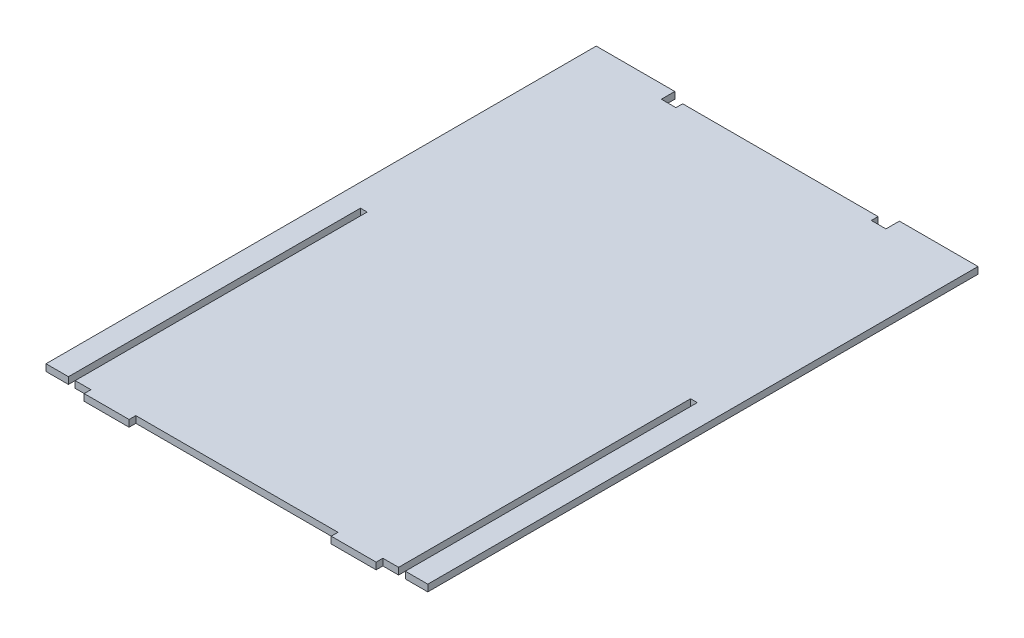
SolidWorks part; units mm, degrees
ref_plane "Front Plane" through (0, 0, 0) normal (0, 0, 1) x (1, 0, 0)
ref_plane "Top Plane" through (0, 0, 0) normal (0, 1, 0) x (1, 0, 0)
ref_plane "Right Plane" through (0, 0, 0) normal (1, 0, 0) x (0, 0, -1)
sketch "Sketch1" plane through (0, 0, 0) normal (0, 1, 0) x (1, 0, 0)
  line L0 (300, 0) -> (300, -6)
  line L2 (0, 0) -> (0, 490)
  line L3 (0, 490) -> (340, 490)
  line L4 (340, 0) -> (340, 490)
  line L5 (300, -6) -> (260, -6)
  line L6 (260, -6) -> (260, 0)
  line L7 (40, 0) -> (40, -6)
  line L8 (40, -6) -> (80, -6)
  line L9 (80, -6) -> (80, 0)
  line L10 (40, 0) -> (0, 0)
  line L11 (80, 0) -> (260, 0)
  line L12 (300, 0) -> (340, 0)
  point P11 (80, -3)
  dimension "D1" = 340
  dimension "D2" = 490
  dimension "D3" = 40
  dimension "D4" = 6
  dimension "D5" = 40
  dimension "D6" = 180
extrude "Boss-Extrude1" add sketch "Sketch1" along normal blind 6
sketch "Sketch2" plane through (0, 6, 0) normal (0, 1, 0) x (1, 0, 0)
  line L1 (20, 0) -> (26, 0)
  line L2 (20, 0) -> (20, 260)
  line L3 (20, 260) -> (26, 260)
  line L4 (26, 0) -> (26, 260)
  line L5 (0, 490) -> (0, 0) construction
  line L6 (0, 0) -> (40, 0) construction
  line L7 (0, 0) -> (40, 0) construction
  dimension "D1" = 260
  dimension "D2" = 6
  dimension "D3" = 20
extrude "Cut-Extrude1" cut sketch "Sketch2" against normal blind 6
pattern_linear "LPattern1" count 2 spacing 294 along (1, 0, 0) of "Cut-Extrude1"
sketch "Sketch3" plane through (0, 6, 0) normal (0, 1, 0) x (1, 0, 0)
  line L3 (340, 490) -> (0, 490) construction
  line L4 (70, 490) -> (270, 490)
  line L18 (70, 490) -> (70, 478)
  line L19 (70, 478) -> (83, 478)
  line L20 (83, 478) -> (83, 484)
  line L21 (270, 490) -> (270, 478)
  line L22 (270, 478) -> (257, 478)
  line L23 (257, 478) -> (257, 484)
  line L24 (83, 484) -> (257, 484)
  line L25 (0, 490) -> (0, 0) construction
  dimension "D1" = 200
  dimension "D2" = 12
  dimension "D3" = 13
  dimension "D4" = 6
  dimension "D5" = 70
extrude "Cut-Extrude2" cut sketch "Sketch3" against normal blind 6
